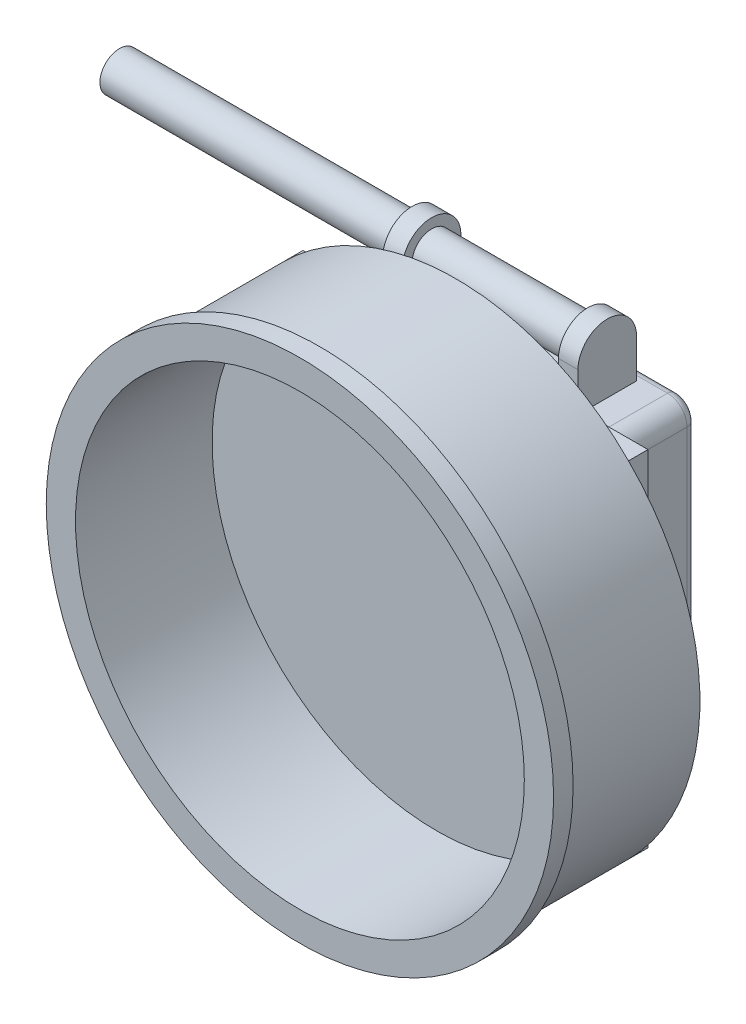
SolidWorks part; units mm, degrees
ref_plane "Front Plane" through (0, 0, 0) normal (0, 0, 1) x (1, 0, 0)
ref_plane "Top Plane" through (0, 0, 0) normal (0, 1, 0) x (1, 0, 0)
ref_plane "Right Plane" through (0, 0, 0) normal (1, 0, 0) x (0, 0, -1)
sketch "Light Sketch" plane through (0, 0, 0) normal (0, 0, 1) x (1, 0, 0)
  circle A0 centre (0, 0) radius 125
  dimension "D1" = 250
extrude "Light Extrude" add sketch "Light Sketch" along normal blind 80
shell "Light Shell" thickness 10 removed face at (125, 0, 80)
sketch "Aperture Lip Sketch" plane through (0, 0, 80) normal (0, 0, 1) x (1, 0, 0)
  circle A0 centre (0, 0) radius 130
  circle A1 centre (0, 0) radius 125 construction
  circle A2 centre (0, 0) radius 115
  circle A3 centre (0, 0) radius 115 construction
  dimension "D1" = 5
extrude "Aperture Lip Extrude" add sketch "Aperture Lip Sketch" against normal blind 10
sketch "Plate Sketch" plane through (0, 0, 0) normal (0, 0, -1) x (-1, 0, 0)
  line L1 (-88.3883, 88.3883) -> (88.3883, 88.3883)
  line L2 (-88.3883, 88.3883) -> (-88.3883, -88.3883)
  line L3 (-88.3883, -88.3883) -> (88.3883, -88.3883)
  line L4 (88.3883, 88.3883) -> (88.3883, -88.3883)
  line L5 (-88.3883, 88.3883) -> (88.3883, -88.3883) construction
  line L6 (-88.3883, -88.3883) -> (88.3883, 88.3883) construction
  circle A0 centre (0, 0) radius 125 construction
  point P0 (0, 0)
extrude "Plate Extrude" add sketch "Plate Sketch" along normal blind 10
sketch "Electronics Sketch" plane through (0, 0, -10) normal (0, 0, -1) x (-1, 0, 0)
  line L0 (88.3883, 88.3883) -> (-88.3883, 88.3883) construction
  line L1 (73.3883, 83.3883) -> (-73.3883, 83.3883)
  line L2 (73.3883, 83.3883) -> (73.3883, -83.3883)
  line L3 (73.3883, -83.3883) -> (-73.3883, -83.3883)
  line L4 (-73.3883, 83.3883) -> (-73.3883, -83.3883)
  line L5 (73.3883, 83.3883) -> (-73.3883, -83.3883) construction
  line L6 (73.3883, -83.3883) -> (-73.3883, 83.3883) construction
  line L7 (88.3883, -88.3883) -> (88.3883, 88.3883) construction
  point P0 (0, 0)
  dimension "D1" = 5
  dimension "D2" = 15
extrude "Electronics Extrude" add sketch "Electronics Sketch" along normal blind 40
fillet "Electronics Back Fillet" radius 5 4 edges at (0, 83.3883, -50) (-73.3883, 0, -50) (0, -83.3883, -50) (73.3883, 0, -50)
fillet "Electronics Side Fillet" radius 10 8 edges at (-71.9239, -81.9239, -48.5355) (-71.9239, 81.9239, -48.5355) (71.9239, 81.9239, -48.5355) (71.9239, -81.9239, -48.5355) (73.3883, -83.3883, -27.5) (73.3883, 83.3883, -27.5) (-73.3883, 83.3883, -27.5) (-73.3883, -83.3883, -27.5)
ref_plane "Hinge Sketch Plane" through (40, 0, 0) normal (1, 0, 0) x (0, 0, -1)
sketch "Hinge Support Sketch" plane through (40, 0, 0) normal (1, 0, 0) x (0, 0, -1)
  line L0 (12.5, 103.3883) -> (12.5, 83.3883)
  line L1 (12.5, 83.3883) -> (42.5, 83.3883)
  line L2 (42.5, 83.3883) -> (42.5, 103.3883)
  line L3 (10, 83.3883) -> (45, 83.3883) construction
  line L4 (12.5, 83.3883) -> (10, 83.3883) construction
  line L5 (42.5, 83.3883) -> (45, 83.3883) construction
  line L6 (10, 88.3883) -> (10, -88.3883) construction
  arc A0 (42.5, 103.3883) -> (12.5, 103.3883) centre (27.5, 103.3883) ccw
  dimension "D1" = 30
  dimension "D2" = 20
extrude "Hinge Support Extrude" add sketch "Hinge Support Sketch" along normal blind 10
mirror "Hinge Support Mirror" about plane through (0, 0, 0) normal (1, 0, 0) of "Hinge Support Extrude"
sketch "Hinge Pole Sketch" plane through (50, 0, 0) normal (1, 0, 0) x (0, 0, -1)
  circle A0 centre (27.5, 103.3883) radius 10
  arc A1 (42.5, 103.3883) -> (12.5, 103.3883) centre (27.5, 103.3883) ccw construction
  dimension "D1" = 20
extrude "Hinge Pole Extrude" add sketch "Hinge Pole Sketch" against normal offset from surface (250 mm away) 150 up to face at (-50, 97.1383, -27.5) offset beyond the face yes
